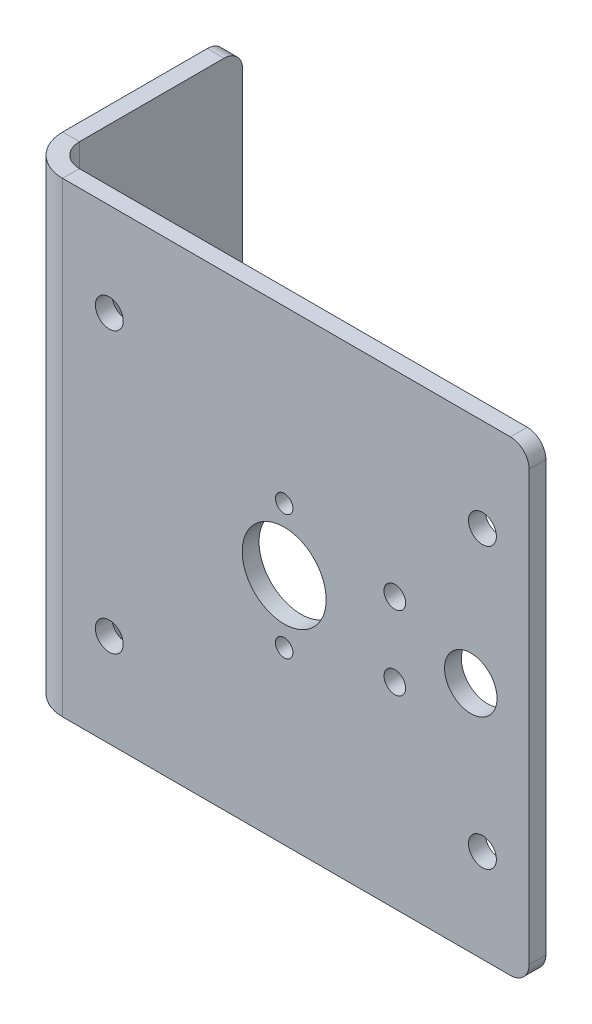
SolidWorks part; units mm, degrees
note: The reader was unsure of these and kept them because the rebuilt part matched: thickness of "Base-Flange1", "Sheet-Metal1", "Sheet-Metal2", "Sheet-Metal3", "Sheet-Metal4", "Sheet-Metal5", "Sheet-Metal7"; bend radius of "Base-Flange1", "BaseBend2".
ref_plane "Front Plane" through (0, 0, 0) normal (1, 0, 0) x (0, 1, 0)
ref_plane "Top Plane" through (0, 0, 0) normal (0, 0, 1) x (0, 1, 0)
ref_plane "Right Plane" through (0, 0, 0) normal (0, 1, 0) x (-1, 0, 0)
sketch "Sketch3" plane through (0, 0, 0) normal (0, 1, 0) x (-1, 0, 0)
  line L0 (-33.3375, 0) -> (33.3375, 0)
  line L2 (33.3375, 0) -> (33.3375, -25.4)
  point P3 (0, 0)
  dimension "D1" = 66.675
  dimension "D3" = 25.4
base flange "Base-Flange1" sketch "Sketch3" end condition mid plane depth 63.5 reverse direction no thickness 2.286 reverse thickness direction yes bend radius 3.175
bend "BaseBend2" bend radius 3.175 bend angle 90 parameters "D5"=1
fillet "Fillet1" radius 2.54 4 edges at (33.3375, -31.75, 1.143) (-34.4805, -31.75, -25.4) (-34.4805, 31.75, -25.4) (33.3375, 31.75, 1.143)
hole_wizard "#25 (0.1495) Diameter Hole1" positions "Sketch8" profile "Sketch9" hole size "#25" standard "ANSI Inch" end condition through all
sketch "Sketch8" plane through (0, 0, 2.286) normal (0, 0, 1) x (1, 0, 0)
  line L0 (1.5875, 0) -> (1.5875, 19.05) construction
  line L1 (1.5875, 19.05) -> (26.9875, 19.05) construction
  line L4 (1.5875, 19.05) -> (-23.8125, 19.05) construction
  line L6 (1.5875, 0) -> (1.5875, -19.05) construction
  line L7 (1.5875, -19.05) -> (-23.8125, -19.05) construction
  line L9 (1.5875, -19.05) -> (26.9875, -19.05) construction
  line L10 (30.7975, 31.75) -> (-30.1625, 31.75) construction
  line L12 (33.3375, 29.21) -> (33.3375, -29.21) construction
  line L13 (30.7975, 31.75) -> (-30.1625, 31.75) construction
  point P0 (-23.8125, 19.05)
  point P2 (26.9875, 19.05)
  point P4 (26.9875, -19.05)
  point P6 (-23.8125, -19.05)
  dimension "D1" = 12.7
  dimension "D2" = 25.4
  dimension "D3" = 31.75
  dimension "D4" = 31.75
sketch "Sketch9" plane through (-23.8125, 19.05, 2.286) normal (1, 0, 0) x (0, -1, 0)
  line L0 (0, 0) -> (0, 27.686)
  line L1 (0, 27.686) -> (1.8986, 27.686)
  line L2 (1.8986, 27.686) -> (1.8986, 0)
  line L5 (1.8986, 0) -> (0, 0)
  line L11 (0, -6.35) -> (0, 107.95) construction
  dimension "Thru Hole Dia." = 3.7973
  dimension "Thru Hole Depth" = 27.686
sketch "Sketch10" plane through (0, 0, 2.286) normal (0, 0, 1) x (1, 0, 0)
  line L0 (33.3375, 0) -> (-33.3375, 0) construction
  line L1 (-22.5183, 0) -> (25.0967, 0) construction
  circle A0 centre (0, 0) radius 5.715
  dimension "D1" = 11.43
extrude "Cut-Extrude1" cut sketch "Sketch10" against normal through all normal cut yes
hole_wizard "9/32 (0.28125) Diameter Hole1" positions "Sketch11" profile "Sketch12" hole size "9/32" standard "ANSI Inch" end condition through all
sketch "Sketch11" plane through (0, 0, 2.286) normal (0, 0, 1) x (1, 0, 0)
  point P0 (25.4, 0)
  dimension "D1" = 25.4
sketch "Sketch12" plane through (25.4, 0, 2.286) normal (1, 0, 0) x (0, -1, 0)
  line L0 (0, 0) -> (0, 27.686)
  line L1 (0, 27.686) -> (3.5719, 27.686)
  line L2 (3.5719, 27.686) -> (3.5719, 0)
  line L5 (3.5719, 0) -> (0, 0)
  line L11 (0, -6.35) -> (0, 107.95) construction
  dimension "Thru Hole Dia." = 7.1437
  dimension "Thru Hole Depth" = 27.686
hole_wizard "3/32 (0.09375) Diameter Hole1" positions "Sketch13" profile "Sketch14" hole size "3/32" standard "ANSI Inch" end condition up to next
sketch "Sketch13" plane through (0, 0, 2.286) normal (0, 0, 1) x (1, 0, 0)
  circle A0 centre (0, 0) radius 8.5
  point P0 (0, 8.5)
  point P2 (0, -8.5)
  dimension "D1" = 17
sketch "Sketch14" plane through (0, 8.5, 2.286) normal (1, 0, 0) x (0, -1, 0)
  line L0 (0, 0) -> (0, 2.286)
  line L1 (0, 2.286) -> (1.1906, 2.286)
  line L2 (1.1906, 2.286) -> (1.1906, 0)
  line L5 (1.1906, 0) -> (0, 0)
  line L11 (0, -6.35) -> (0, 107.95) construction
  dimension "Thru Hole Dia." = 2.3812
  dimension "Thru Hole Depth" = 2.286
sketch "Sketch15" plane through (0, 0, 2.286) normal (0, 0, 1) x (1, 0, 0)
  line L0 (0, 0) -> (16.4978, 9.525) construction
  line L1 (16.4978, 9.525) -> (16.4978, -9.525) construction
  line L2 (16.4978, -9.525) -> (0, 0) construction
  circle A0 centre (0, 0) radius 19.05
  point P3 (15.0579, 5.0275)
  point P4 (15.0579, -5.0275)
  dimension "D1" = 38.1
  dimension "D2" = 19.05
  dimension "D3" = 3.175
  dimension "D4" = 3.175
  dimension "D5" = 15.875
  dimension "D6" = 15.875
hole_wizard "#32 (0.116) Diameter Hole1" positions "Sketch18" profile "Sketch19" hole size "#32" standard "ANSI Inch" end condition through all
sketch "Sketch18" plane through (0, 0, 2.286) normal (0, 0, 1) x (1, 0, 0)
  point P0 (15.0579, 5.0275)
  point P3 (15.0579, -5.0275)
sketch "Sketch19" plane through (15.0579, 5.0275, 2.286) normal (1, 0, 0) x (0, -1, 0)
  line L0 (0, 0) -> (0, 27.686)
  line L1 (0, 27.686) -> (1.4732, 27.686)
  line L2 (1.4732, 27.686) -> (1.4732, 0)
  line L5 (1.4732, 0) -> (0, 0)
  line L11 (0, -6.35) -> (0, 107.95) construction
  dimension "Thru Hole Dia." = 2.9464
  dimension "Thru Hole Depth" = 27.686
sketch "Bend-Lines1" [suppressed] plane through (0, 0, 0) normal (0, 1, 0) x (1, 0, 0)
sketch "Bounding-Box1" [suppressed] plane through (0, 0, 0) normal (0, 1, 0) x (1, 0, 0)
sheet metal parameters "Sheet-Metal1" thickness 2.286 parameters "D1"=3.175
flat pattern "Flat-Pattern1" [suppressed]
sketch "Bend-Lines2" plane through (0, 0, 0) normal (0, 1, 0) x (1, 0, 0)
sketch3d "Bounding-Box2" [suppressed]
  line L0 (-63.5, -63.5, 0) -> (0, -63.5, 0) construction
  line L1 (-63.5, 0, 0) -> (0, 0, 0) construction
  line L2 (-63.5, -63.5, 0) -> (-63.5, 0, 0) construction
  line L3 (0, -63.5, 0) -> (0, 0, 0) construction
bend of the flat pattern "Flatten-<BaseBend2>1"
sheet metal parameters "Sheet-Metal2" thickness 2.286 parameters "D1"=3.175, "D7"=1.5875
flat pattern "Flat-Pattern1" [suppressed]
sketch "Bend-Lines2" plane through (0, 0, 0) normal (0, 1, 0) x (1, 0, 0)
sketch3d "Bounding-Box2" [suppressed]
  line L0 (-63.5, -63.5, 0) -> (0, -63.5, 0) construction
  line L1 (-63.5, 0, 0) -> (0, 0, 0) construction
  line L2 (-63.5, -63.5, 0) -> (-63.5, 0, 0) construction
  line L3 (0, -63.5, 0) -> (0, 0, 0) construction
bend of the flat pattern "Flatten-<BaseBend2>2"
sheet metal parameters "Sheet-Metal3" thickness 2.286 parameters "D1"=3.175, "D7"=1.5875
flat pattern "Flat-Pattern1" [suppressed]
sketch "Bend-Lines2" plane through (0, 0, 0) normal (0, 1, 0) x (1, 0, 0)
sketch3d "Bounding-Box2" [suppressed]
  line L0 (-63.5, -63.5, 0) -> (0, -63.5, 0) construction
  line L1 (-63.5, 0, 0) -> (0, 0, 0) construction
  line L2 (-63.5, -63.5, 0) -> (-63.5, 0, 0) construction
  line L3 (0, -63.5, 0) -> (0, 0, 0) construction
bend of the flat pattern "Flatten-<BaseBend2>3"
sheet metal parameters "Sheet-Metal4" thickness 2.286 parameters "D1"=3.175, "D7"=1.5875
flat pattern "Flat-Pattern1" [suppressed]
sketch "Bend-Lines2" plane through (0, 0, 2.286) normal (0, 0, 1) x (1, 0, 0)
  line L0 (33.5538, 31.75) -> (33.5538, -31.75) construction
  line L1 (33.5538, 31.75) -> (33.5538, -31.75) construction
sketch3d "Bounding-Box2" [suppressed]
  line L0 (-66.675, -63.5, 0) -> (13.1327, -63.5, 0) construction
  line L1 (-66.675, 0, 0) -> (13.1327, 0, 0) construction
  line L2 (-66.675, -63.5, 0) -> (-66.675, 0, 0) construction
  line L3 (13.1327, -63.5, 0) -> (13.1327, 0, 0) construction
bend of the flat pattern "Flatten-<BaseBend2>4"
sheet metal parameters "Sheet-Metal5" thickness 2.286 parameters "D1"=3.175, "D7"=1.5875
flat pattern "Flat-Pattern1"
sketch "Bend-Lines2" plane through (0, 0, 2.286) normal (0, 0, 1) x (1, 0, 0)
  line L2 (-33.5538, -31.75) -> (-33.5538, 31.75) construction
  line L3 (-33.5538, -31.75) -> (-33.5538, 31.75) construction
sketch3d "Bounding-Box2" [suppressed]
  line L0 (-92.5077, -63.5, 0) -> (0, -63.5, 0) construction
  line L1 (-92.5077, 0, 0) -> (0, 0, 0) construction
  line L2 (-92.5077, -63.5, 0) -> (-92.5077, 0, 0) construction
  line L3 (0, -63.5, 0) -> (0, 0, 0) construction
bend of the flat pattern "Flatten-<BaseBend2>5"
sheet metal parameters "Sheet-Metal7" thickness 2.286 parameters "D1"=3.175, "D7"=1.5875
flat pattern "Flat-Pattern1"
sketch "Bend-Lines2" plane through (0, 0, 2.286) normal (0, 0, 1) x (1, 0, 0)
  line L2 (-33.5538, -31.75) -> (-33.5538, 31.75) construction
  line L3 (-33.5538, -31.75) -> (-33.5538, 31.75) construction
sketch3d "Bounding-Box2" [suppressed]
  line L0 (-92.5077, -63.5, 0) -> (0, -63.5, 0) construction
  line L1 (-92.5077, 0, 0) -> (0, 0, 0) construction
  line L2 (-92.5077, -63.5, 0) -> (-92.5077, 0, 0) construction
  line L3 (0, -63.5, 0) -> (0, 0, 0) construction
bend of the flat pattern "Flatten-<BaseBend2>5"
